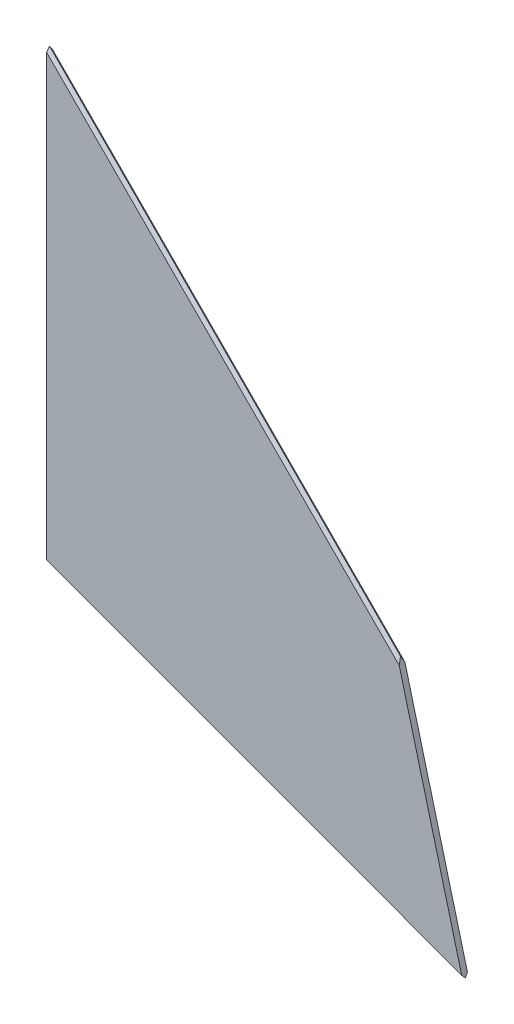
SolidWorks part; units mm, degrees
material "Carbon Fiber"
ref_plane "Front Plane" through (0, 0, 0) normal (0, 0, 1) x (1, 0, 0)
ref_plane "Top Plane" through (0, 0, 0) normal (0, 1, 0) x (1, 0, 0)
ref_plane "Right Plane" through (0, 0, 0) normal (1, 0, 0) x (0, 0, -1)
sketch "Sketch1" plane through (0, 0, 0) normal (0, 0, 1) x (1, 0, 0)
  line L0 (0, 0) -> (0, 234)
  line L1 (0, 234) -> (184, 49)
  line L2 (184, 49) -> (218, -80)
  line L3 (0, 0) -> (218, -80)
  dimension "D1" = 234
  dimension "D2" = 184
  dimension "D3" = 185
  dimension "D4" = 314
  dimension "D5" = 218
extrude "Boss-Extrude1" add sketch "Sketch1" along normal mid plane 3
chamfer "Chamfer1" distance 1.5 angle 45 4 edges at (92, 141.5, -1.5) (92, 141.5, 1.5) (109, -40, -1.5) (109, -40, 1.5)
sketch "Sketch3" plane through (0, 0, 0) normal (0, 1, 0) x (1, 0, 0)
  line L0 (0, 0) -> (-1, 0) construction
  line L2 (0, 0) -> (0, 20)
  line L3 (0, 20) -> (-4.4315, 20)
  line L6 (0, 0) -> (0, -20)
  line L7 (0, -20) -> (-4.4315, -20)
  arc A0 (-4.4315, -20) -> (-4.4315, 20) centre (-61, 0) ccw
  dimension "D1" = 120
  dimension "D2" = 40
  dimension "D3" = 1
extrude "Boss-Extrude2" [suppressed] add sketch "Sketch3" along normal up to vertex (235.6266 mm away) contours L3 A0 L7 L6 L2
fillet "Fillet1" [suppressed] radius 37
fillet "Fillet3" [suppressed] radius 18
